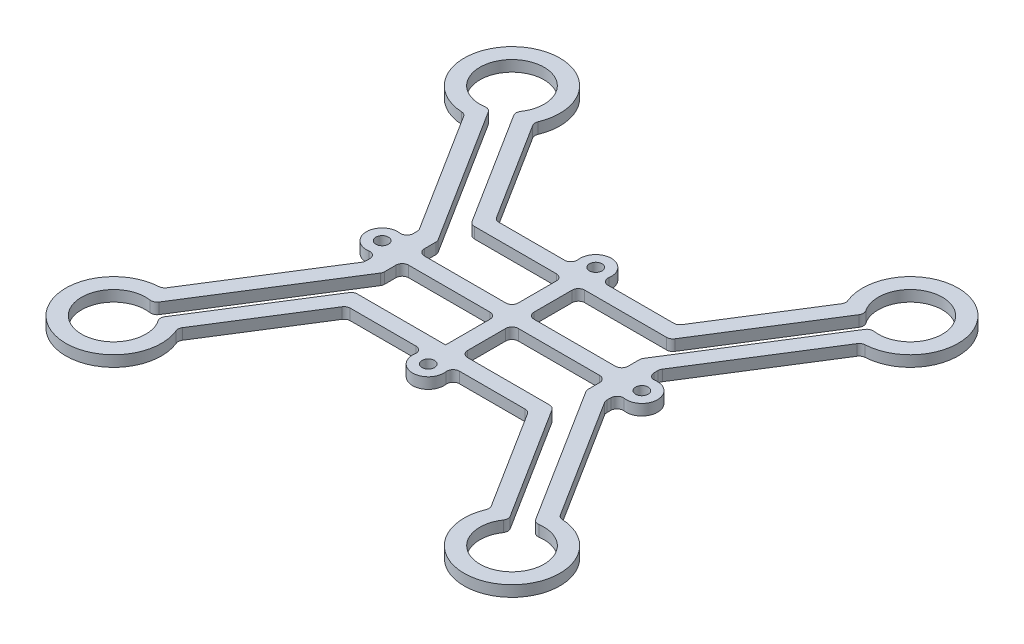
SolidWorks part; units mm, degrees
material "Hexcel AS4C (3000 Filaments)"
ref_plane "Front Plane" through (0, 0, 0) normal (0, 0, 1) x (1, 0, 0)
ref_plane "Top Plane" through (0, 0, 0) normal (0, 1, 0) x (1, 0, 0)
ref_plane "Right Plane" through (0, 0, 0) normal (1, 0, 0) x (0, 0, -1)
sketch "Sketch1" plane through (0, 0, 0) normal (0, 1, 0) x (1, 0, 0)
  line L0 (0, 28.7416) -> (0, -31.95) construction
  line L1 (-19.25, 11.875) -> (19.25, 11.875)
  line L2 (-19.25, 11.875) -> (-19.25, -11.875)
  line L3 (-19.25, -11.875) -> (19.25, -11.875)
  line L4 (19.25, 11.875) -> (19.25, -11.875)
  line L5 (-19.25, 11.875) -> (19.25, -11.875) construction
  line L6 (-19.25, -11.875) -> (19.25, 11.875) construction
  line L7 (-23.7954, 0) -> (45.7192, 0) construction
  line L8 (-31.8198, 4.3198) -> (-31.8198, -4.3198) construction
  line L9 (-31.8198, -31.8198) -> (-31.8198, 31.8198) construction
  line L10 (-31.8198, 31.8198) -> (-19.25, 11.875) construction
  line L11 (19.25, 9.825) -> (-13.5, 9.825)
  line L12 (19.25, 9.825) -> (19.25, -9.825)
  line L13 (19.25, -9.825) -> (-13.5, -9.825)
  line L14 (-13.5, 9.825) -> (-13.5, -9.825)
  line L15 (19.25, 9.825) -> (-13.5, -9.825) construction
  line L16 (19.25, -9.825) -> (-13.5, 9.825) construction
  line L17 (-31.727, 24.1704) -> (-19.25, 4.3728)
  line L18 (-24.959, 28.4358) -> (-14.5219, 11.875)
  line L19 (-35.2038, 29.6871) -> (-22.634, 9.7423) construction
  line L20 (-28.4358, 33.9525) -> (-15.866, 14.0077) construction
  line L21 (24.959, 28.4358) -> (14.5219, 11.875)
  line L22 (31.727, 24.1704) -> (19.25, 4.3728)
  line L23 (24.959, -28.4358) -> (14.5219, -11.875)
  line L24 (31.727, -24.1704) -> (19.25, -4.3728)
  line L25 (-24.959, -28.4358) -> (-14.5219, -11.875)
  line L26 (-31.727, -24.1704) -> (-19.25, -4.3728)
  line L27 (-31.8198, 31.8198) -> (31.8198, 31.8198) construction
  circle A0 centre (-31.8198, 31.8198) radius 27.5
  circle A1 centre (31.8198, 31.8198) radius 27.5
  circle A2 centre (-31.8198, -31.8198) radius 27.5
  circle A3 centre (31.8198, -31.8198) radius 27.5
  circle A4 centre (-31.8198, 31.8198) radius 7.65
  circle A5 centre (-31.8198, 31.8198) radius 5.125
  circle A6 centre (31.8198, 31.8198) radius 5.125
  circle A7 centre (31.8198, 31.8198) radius 7.65
  circle A8 centre (31.8198, -31.8198) radius 5.125
  circle A9 centre (31.8198, -31.8198) radius 7.65
  circle A10 centre (-31.8198, -31.8198) radius 5.125
  circle A11 centre (-31.8198, -31.8198) radius 7.65
  point P0 (0, 0)
  point P18 (2.875, 0)
  dimension "D3" = 55
  dimension "D8" = 15.3
  dimension "D9" = 10.25
  dimension "D1" = 23.75
  dimension "D2" = 38.5
  dimension "D4" = 19.65
  dimension "D5" = 32.75
  dimension "D10" = 8
  dimension "D6" = 90
extrude "Boss-Extrude1" add sketch "Sketch1" along normal blind 1.75 contours A4 A5 | A4 L17 L2 L1 L18 | A11 A10 | L26 A11 L25 L3 L2 | A9 A8 | A9 L24 L4 L3 L23 | A7 A6 | L22 A7 L21 L1 L4 | L26 A2 L2 | A0 L17 L2 | A3 L24 L4 | L22 A1 L12 | L1 L4 L3 L2 region at (-23.128, 0, -17.8619) region at (-19.7311, 0, -6.1292) region at (-27.8564, 0, -25.5309) region at (-19.7311, 0, 6.1292) region at (23.128, 0, -17.8619) region at (-23.128, 0, 17.8619) region at (30.1315, 0, -39.0592) region at (19.7311, 0, -6.1292) region at (-27.8564, 0, 25.5309) region at (19.7311, 0, 6.1292) region at (23.128, 0, 17.8619) region at (27.8564, 0, 25.5309)
sketch "Sketch2" plane through (0, 1.75, 0) normal (0, 1, 0) x (1, 0, 0)
  line L0 (-19.25, 0) -> (19.25, 0) construction
  line L1 (-19.25, 4.3728) -> (-19.25, -4.3728) construction
  line L2 (19.25, 4.3728) -> (19.25, -4.3728) construction
  line L3 (0, 11.875) -> (0, -11.875) construction
  line L4 (-14.5219, 11.875) -> (14.5219, 11.875) construction
  line L5 (-14.5219, -11.875) -> (14.5219, -11.875) construction
  line L6 (-29.0873, 27.484) -> (-11.766, 0) construction
  line L7 (-31.727, 24.1704) -> (-19.25, 4.3728) construction
  line L8 (-24.959, 28.4358) -> (-14.5219, 11.875) construction
  line L9 (-30.4507, 26.881) -> (-16.2654, 4.3728)
  line L10 (-31.8198, 36.9448) -> (-31.8198, 39.4698) construction
  line L11 (-23.3581, 15.6269) -> (-25.4942, 14.2807) construction
  line L12 (-19.25, 4.3728) -> (19.25, 4.3728) construction
  line L13 (-27.955, 28.4539) -> (-12.7784, 4.3728)
  line L14 (-15.9152, 9.35) -> (15.9152, 9.35)
  line L15 (0, 9.35) -> (0, 11.875) construction
  line L16 (-16.2654, 4.3728) -> (-16.2654, -4.3728)
  line L17 (-12.7784, 4.3728) -> (-12.7784, -4.3728)
  line L18 (12.7784, 4.3728) -> (12.7784, -4.3728)
  line L19 (16.2654, 4.3728) -> (16.2654, -4.3728)
  line L20 (27.955, 28.4539) -> (12.7784, 4.3728)
  line L21 (30.4507, 26.881) -> (16.2654, 4.3728)
  line L22 (27.955, -28.4539) -> (12.7784, -4.3728)
  line L23 (30.4507, -26.881) -> (16.2654, -4.3728)
  line L24 (-15.9152, -9.35) -> (15.9152, -9.35)
  line L25 (-30.4507, -26.881) -> (-16.2654, -4.3728)
  line L26 (-27.955, -28.4539) -> (-12.7784, -4.3728)
  line L27 (-1.2625, 0) -> (1.2625, 0) construction
  line L28 (1.2625, -9.35) -> (-1.2625, -9.35)
  line L29 (1.2625, -9.35) -> (1.2625, 9.35)
  line L30 (1.2625, 9.35) -> (-1.2625, 9.35)
  line L31 (-1.2625, -9.35) -> (-1.2625, 9.35)
  line L32 (1.2625, -9.35) -> (-1.2625, 9.35) construction
  line L33 (1.2625, 9.35) -> (-1.2625, -9.35) construction
  line L35 (-16.2654, -1.2625) -> (16.2654, -1.2625)
  line L36 (-16.2654, -1.2625) -> (-16.2654, 1.2625)
  line L37 (-16.2654, 1.2625) -> (16.2654, 1.2625)
  line L38 (16.2654, -1.2625) -> (16.2654, 1.2625)
  line L39 (-16.2654, -1.2625) -> (16.2654, 1.2625) construction
  line L40 (-16.2654, 1.2625) -> (16.2654, -1.2625) construction
  circle A0 centre (-31.8198, 31.8198) radius 5.125 construction
  circle A1 centre (-31.8198, 31.8198) radius 5.125
  circle A2 centre (31.8198, 31.8198) radius 5.125
  arc A3 (-24.959, 28.4358) -> (-31.727, 24.1704) centre (-31.8198, 31.8198) ccw construction
  circle A4 centre (-31.8198, -31.8198) radius 5.125
  circle A5 centre (31.8198, -31.8198) radius 5.125
  point P39 (0, 0)
  point P41 (0, 0)
  point P42 (-16.2654, 0)
  point P45 (12.7784, 0)
  point P47 (0, 9.35)
  point P60 (16.2654, 0)
  point P66 (-12.7784, 0)
extrude "Cut-Extrude2" cut sketch "Sketch2" against normal up to next contours L16 L37 L17 L13 L33 L9 | L17 L37 L31 L14 L13 | L29 L37 L18 L20 L14 | L18 L37 L19 L21 L36 L20 | L35 L18 L22 L23 L19 | L35 L29 L24 L22 L18 | L35 L17 L26 L24 L31 | L35 L16 L25 L32 L26 L17 region at (-20.9447, 1.75, -14.4076) region at (-7.5466, 1.75, -5.4907) region at (-20.9447, 1.75, 14.4076) region at (-7.5466, 1.75, 5.4907) region at (7.5466, 1.75, -5.4907) region at (20.9447, 1.75, -14.4076) region at (7.5466, 1.75, 5.4907) region at (20.9447, 1.75, 14.4076)
fillet "Fillet1" radius 1 43 edges at (-30.4507, 0.875, 26.881) (-31.727, 0.875, -24.1704) (-1.2625, 0.875, -1.2625) (1.2625, 0.875, -1.2625) (-16.2654, 0.875, -1.2625) (-1.2625, 0.875, 1.2625) (-1.2625, 0.875, -9.35) (-31.727, 0.875, 24.1704) (-19.25, 0.875, 4.3728) (-19.25, 0.875, -4.3728) (24.959, 0.875, -28.4358) (-27.955, 0.875, -28.4539) (-27.955, 0.875, 28.4539) (-14.5219, 0.875, -11.875) (-15.9152, 0.875, 9.35) (-30.4507, 0.875, -26.881) (-24.959, 0.875, -28.4358) (-15.9152, 0.875, -9.35) (-16.2654, 0.875, -4.3728) (-16.2654, 0.875, 4.3728) (-16.2654, 0.875, 1.2625) (1.2625, 0.875, -9.35) (1.2625, 0.875, 1.2625) (1.2625, 0.875, 9.35) (16.2654, 0.875, -1.2625) (16.2654, 0.875, -4.3728) (15.9152, 0.875, -9.35) (14.5219, 0.875, -11.875) (30.4507, 0.875, -26.881) (27.955, 0.875, -28.4539) (31.727, 0.875, -24.1704) (19.25, 0.875, -4.3728) (16.2654, 0.875, 1.2625) (16.2654, 0.875, 4.3728) (15.9152, 0.875, 9.35) (19.25, 0.875, 4.3728) (31.727, 0.875, 24.1704) (30.4507, 0.875, 26.881) (27.955, 0.875, 28.4539) (24.959, 0.875, 28.4358) (14.5219, 0.875, 11.875) (-14.5219, 0.875, 11.875) (-24.959, 0.875, 28.4358)
sketch "Sketch4" plane through (0, 0, 0) normal (0, -1, 0) x (1, 0, 0)
  line L0 (-28.6014, 0) -> (31.9252, 0) construction
  line L1 (0, -23.8326) -> (0, 22.253) construction
  line L2 (-13.9701, -11.875) -> (13.9701, -11.875) construction
  line L3 (-0.866, -11.875) -> (-1.7321, -13.375)
  line L4 (-1.7321, -13.375) -> (-0.866, -14.875)
  line L5 (-0.866, -14.875) -> (0.866, -14.875)
  line L6 (0.866, -14.875) -> (1.7321, -13.375)
  line L7 (1.7321, -13.375) -> (0.866, -11.875)
  line L8 (0.866, -11.875) -> (-0.866, -11.875)
  line L9 (-2.5, -13.375) -> (-2.5, -11.875) construction
  line L10 (-20.75, -2.5) -> (-19.25, -2.5) construction
  line L11 (-19.25, -4.084) -> (-19.25, 4.084) construction
  circle A0 centre (0, -13.375) radius 1
  circle A1 centre (0, -13.375) radius 2.5
  circle A2 centre (0, -13.375) radius 1.5 construction
  circle A3 centre (0, 13.375) radius 2.5
  circle A4 centre (0, 13.375) radius 1
  circle A5 centre (-20.75, 0) radius 1
  circle A6 centre (-20.75, 0) radius 2.5
  circle A7 centre (20.75, 0) radius 1
  circle A8 centre (20.75, 0) radius 2.5
  dimension "D1" = 2
  dimension "D2" = 5
  dimension "D3" = 3
extrude "Boss-Extrude2" add sketch "Sketch4" against normal up to surface (1.75 mm away) contours A6 A5 | A1 L8 L7 L6 L5 L4 L3 | L7 L8 L3 L4 L5 L6 A0 | A3 A4 | A8 A7 region at (0, 0, -11.9208) region at (-2.4293, 0, -13.375) region at (-2.4293, 0, 13.375) region at (-23.1793, 0, 0) region at (18.3207, 0, 0) up to face at (16.0204, 1.75, -12.188)
fillet "Fillet2" radius 1 8 edges at (-2, 0.875, 11.875) (2, 0.875, 11.875) (2, 0.875, -11.875) (-2, 0.875, -11.875) (-19.25, 0.875, -2) (-19.25, 0.875, 2) (19.25, 0.875, 2) (19.25, 0.875, -2)
equation "\"PropDiameter\"=55"
equation "\"D3@Sketch1\"=\"PropDiameter\""
